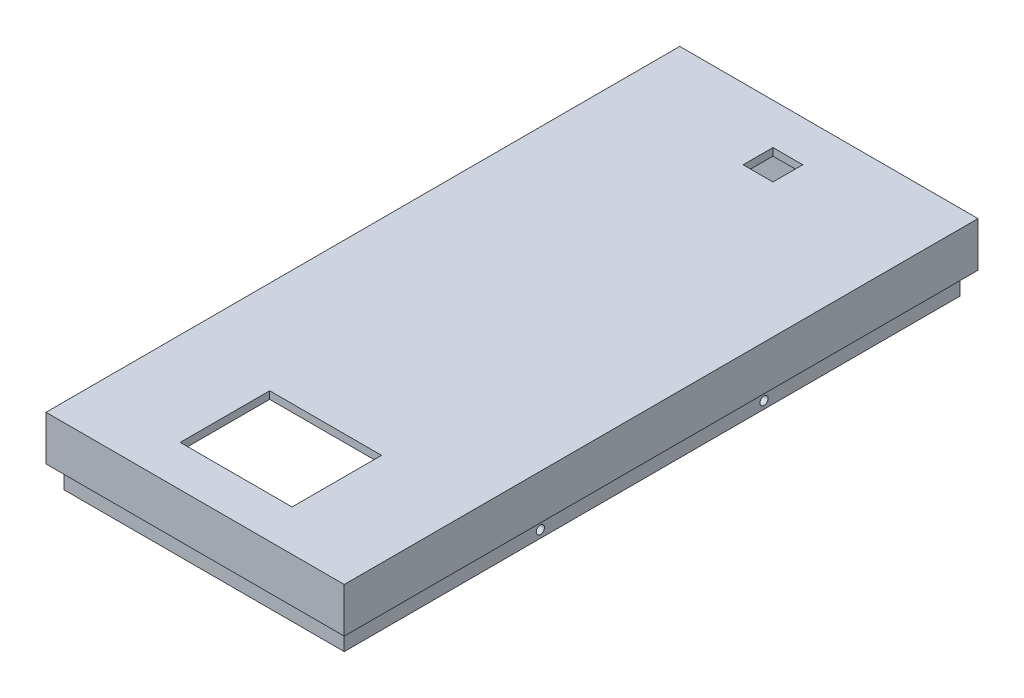
SolidWorks part; units mm, degrees
ref_plane "Front Plane" through (0, 0, 0) normal (0, 0, 1) x (1, 0, 0)
ref_plane "Top Plane" through (0, 0, 0) normal (0, 1, 0) x (1, 0, 0)
ref_plane "Right Plane" through (0, 0, 0) normal (1, 0, 0) x (0, 0, -1)
sketch "Sketch1" plane through (0, 0, 0) normal (0, 0, 1) x (1, 0, 0)
  line L1 (-40, 34) -> (40, 34)
  line L2 (-40, 34) -> (-40, 46)
  line L3 (-40, 46) -> (40, 46)
  line L4 (40, 34) -> (40, 46)
extrude "Boss-Extrude1" add sketch "Sketch1" along normal blind 170 from offset 85 offset against normal yes
sketch "Sketch2" plane through (0, 0, 0) normal (0, 0, 1) x (1, 0, 0)
  line L1 (-38, 30) -> (38, 30)
  line L2 (-38, 30) -> (-38, 44)
  line L3 (-38, 44) -> (38, 44)
  line L4 (38, 30) -> (38, 44)
extrude "Boss-Extrude2" add sketch "Sketch2" along normal blind 166 from offset 83 separate body offset against normal yes
combine bodies "Combine1" operation type subtract main body 101 bodies to subtract 102
sketch "Sketch3" plane through (0, 0, 0) normal (0, 0, 1) x (1, 0, 0)
  line L1 (-37.6, 28) -> (37.6, 28)
  line L2 (-37.6, 28) -> (-37.6, 44.5)
  line L3 (-37.6, 44.5) -> (37.6, 44.5)
  line L4 (37.6, 28) -> (37.6, 44.5)
extrude "Boss-Extrude3" add sketch "Sketch3" along normal blind 165.2 from offset 82.6 offset against normal yes
sketch "Sketch4" plane through (0, 0, 0) normal (0, 0, 1) x (1, 0, 0)
  line L1 (-35.6, 27) -> (35.6, 27)
  line L2 (-35.6, 27) -> (-35.6, 44)
  line L3 (-35.6, 44) -> (35.6, 44)
  line L4 (35.6, 27) -> (35.6, 44)
extrude "Boss-Extrude4" add sketch "Sketch4" along normal blind 161.2 from offset 80.6 separate body offset against normal yes
combine bodies "Combine2" operation type subtract main body 104 bodies to subtract 105
sketch "Sketch5" plane through (0, 0, 0) normal (0, 0, 1) x (1, 0, 0)
  line L1 (-15, 40) -> (15, 40)
  line L2 (-15, 40) -> (-15, 50)
  line L3 (-15, 50) -> (15, 50)
  line L4 (15, 40) -> (15, 50)
extrude "Boss-Extrude5" add sketch "Sketch5" along normal blind 24 from offset 50 separate body
combine bodies "Combine3" operation type subtract main body 106 bodies to subtract 107
sketch "Sketch6" plane through (0, 0, 0) normal (0, 0, 1) x (1, 0, 0)
  line L1 (-4, 40) -> (4, 40)
  line L2 (-4, 40) -> (-4, 50)
  line L3 (-4, 50) -> (4, 50)
  line L4 (4, 40) -> (4, 50)
extrude "Boss-Extrude6" add sketch "Sketch6" along normal blind 8 from offset 74 separate body offset against normal yes
combine bodies "Combine4" operation type subtract main body 108 bodies to subtract 109
sketch "Sketch7" plane through (0, 0, 0) normal (1, 0, 0) x (0, 0, -1)
  circle A0 centre (30, 30) radius 1.1
extrude "Boss-Extrude7" add sketch "Sketch7" along normal blind 90 from offset 45 separate body offset against normal yes
combine bodies "Combine5" operation type subtract main body 110 bodies to subtract 111
sketch "Sketch8" plane through (0, 0, 0) normal (1, 0, 0) x (0, 0, -1)
  circle A0 centre (-30, 30) radius 1.1
extrude "Boss-Extrude8" add sketch "Sketch8" along normal blind 90 from offset 45 separate body offset against normal yes
combine bodies "Combine6" operation type subtract main body 112 bodies to subtract 113
